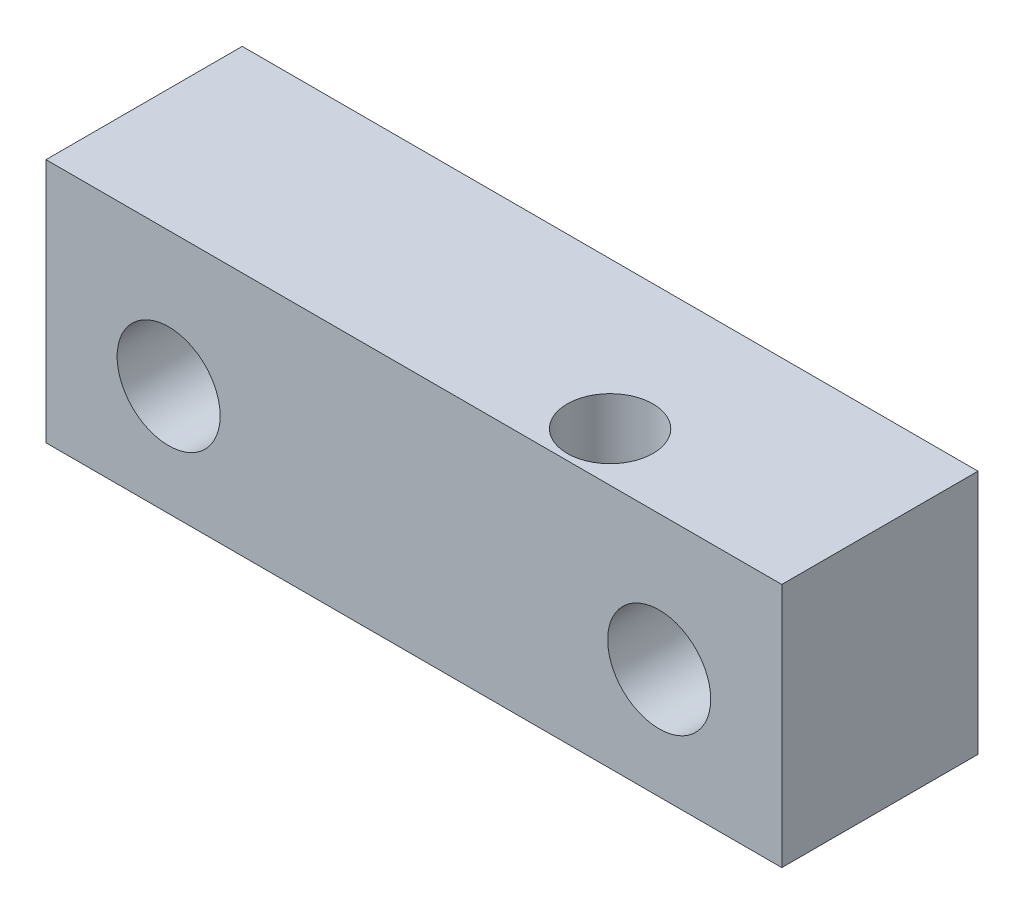
SolidWorks part; units mm, degrees
ref_plane "Front Plane" through (0, 0, 0) normal (0, 0, 1) x (1, 0, 0)
ref_plane "Top Plane" through (0, 0, 0) normal (0, 1, 0) x (1, 0, 0)
ref_plane "Right Plane" through (0, 0, 0) normal (1, 0, 0) x (0, 0, -1)
sketch "Sketch1" plane through (0, 0, 0) normal (0, 1, 0) x (1, 0, 0)
  line L0 (6, -2) -> (6, -4) construction
  line L5 (-15, 4) -> (15, 4)
  line L6 (-15, 4) -> (-15, -4)
  line L7 (-15, -4) -> (15, -4)
  line L8 (15, 4) -> (15, -4)
  line L9 (-15, 4) -> (15, -4) construction
  line L10 (-15, -4) -> (15, 4) construction
  line L11 (0, 0) -> (6, 0) construction
  circle A0 centre (6, -2) radius 1.75
  point P0 (0, 0)
  point P8 (0, 0)
  point P11 (0, -2)
  point P13 (0, 0)
  point P14 (0, 0)
  point P15 (0, 0)
  point P16 (0, 0)
  point P17 (0, 0)
  point P18 (6, -4)
  dimension "D3" = 3.5
  dimension "D1" = 30
  dimension "D2" = 8
  dimension "D4" = 2
  dimension "D5" = 6
extrude "Boss-Extrude1" add sketch "Sketch1" along normal blind 2
sketch "Sketch2" plane through (0, 0, 4) normal (0, 0, 1) x (1, 0, 0)
  line L0 (-10, -3.5) -> (10, -3.5) construction
  line L2 (-15, 0) -> (-15, -8)
  line L5 (15, 0) -> (5, 0)
  line L6 (15, 0) -> (15, -8)
  line L7 (15, -8) -> (-15, -8)
  line L9 (-15, 0) -> (5, 0)
  line L10 (-15, 2) -> (15, 2) construction
  line L11 (-15, 0) -> (15, 0) construction
  circle A0 centre (-10, -3.5) radius 2.1
  circle A1 centre (10, -3.5) radius 2.1
  point P13 (10, 0)
  point P17 (0, -3.5)
  point P22 (0, 0)
  dimension "D1" = 4.2
  dimension "D2" = 4.2
  dimension "D3" = 5.5
  dimension "D4" = 8
  dimension "D5" = 20
extrude "Boss-Extrude2" add sketch "Sketch2" against normal up to surface (8 mm away) up to face at (0, 1, -4)
sketch "Sketch4" plane through (0, 0, 0) normal (0, 1, 0) x (1, 0, 0)
  circle A1 centre (6, -2) radius 1.75
  circle A2 centre (6, -2) radius 1.75
  dimension "D1" = 0
extrude "Cut-Extrude2" cut sketch "Sketch4" against normal offset from surface (2 mm away) 4 up to face at (0, 2, 0)
sketch "Sketch5" plane through (0, 0, -4) normal (0, 0, -1) x (-1, 0, 0)
  line L0 (15, 2) -> (15, -8) construction
  line L1 (-15, -8) -> (15, -8)
  line L2 (-15, -8) -> (-15, 0)
  line L3 (-15, 0) -> (15, 0)
  line L4 (15, -8) -> (15, 0)
extrude "Boss-Extrude3" add sketch "Sketch5" against normal offset from surface (4 mm away) 4 up to face at (0, -3, 4)
